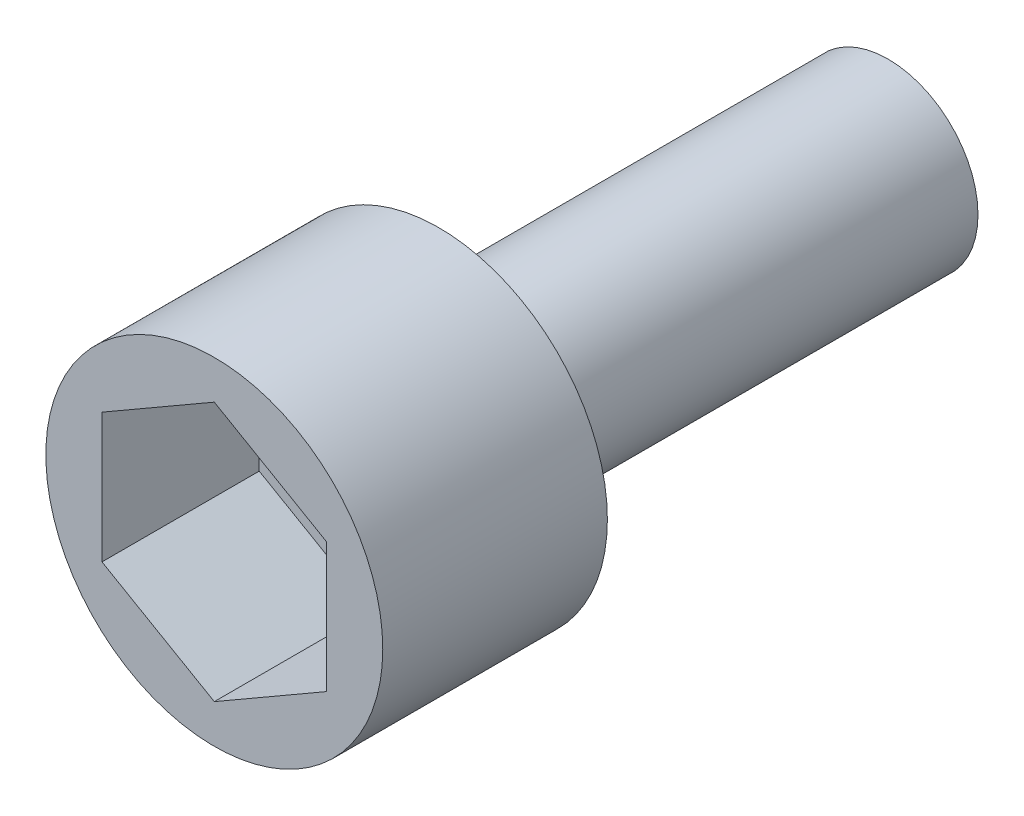
SolidWorks part; units mm, degrees
material "AISI 304"
ref_plane "Front Plane" through (0, 0, 0) normal (0, 0, 1) x (1, 0, 0)
ref_plane "Top Plane" through (0, 0, 0) normal (0, 1, 0) x (1, 0, 0)
ref_plane "Right Plane" through (0, 0, 0) normal (1, 0, 0) x (0, 0, -1)
sketch "Sketch1" plane through (0, 0, 0) normal (0, 0, 1) x (1, 0, 0)
  line L1 (0, 5.7735) -> (-5, 2.8868)
  line L2 (-5, 2.8868) -> (-5, -2.8868)
  line L3 (-5, -2.8868) -> (0, -5.7735)
  line L4 (0, -5.7735) -> (5, -2.8868)
  line L5 (5, -2.8868) -> (5, 2.8868)
  line L6 (5, 2.8868) -> (0, 5.7735)
  circle A0 centre (0, 0) radius 5 construction
  circle A1 centre (0, 0) radius 4
  circle A2 centre (0, 0) radius 7.5
  point P11 (0, 0)
  dimension "D1" = 15
  dimension "D2" = 8
  dimension "D3" = 10
extrude "Boss-Extrude1" add sketch "Sketch1" against normal blind 10 contours A2
extrude "Boss-Extrude2" add sketch "Sketch1<3>" against normal blind 30 contours A1
sketch "Sketch1<3>" plane through (0, 0, 0) normal (0, 0, 1) x (1, 0, 0) same geometry as "Sketch1"
extrude "Cut-Extrude1" cut sketch "Sketch1<4>" against normal blind 7 contours L6 L1 L2 L3 L4 L5
sketch "Sketch1<4>" plane through (0, 0, 0) normal (0, 0, 1) x (1, 0, 0) same geometry as "Sketch1"
